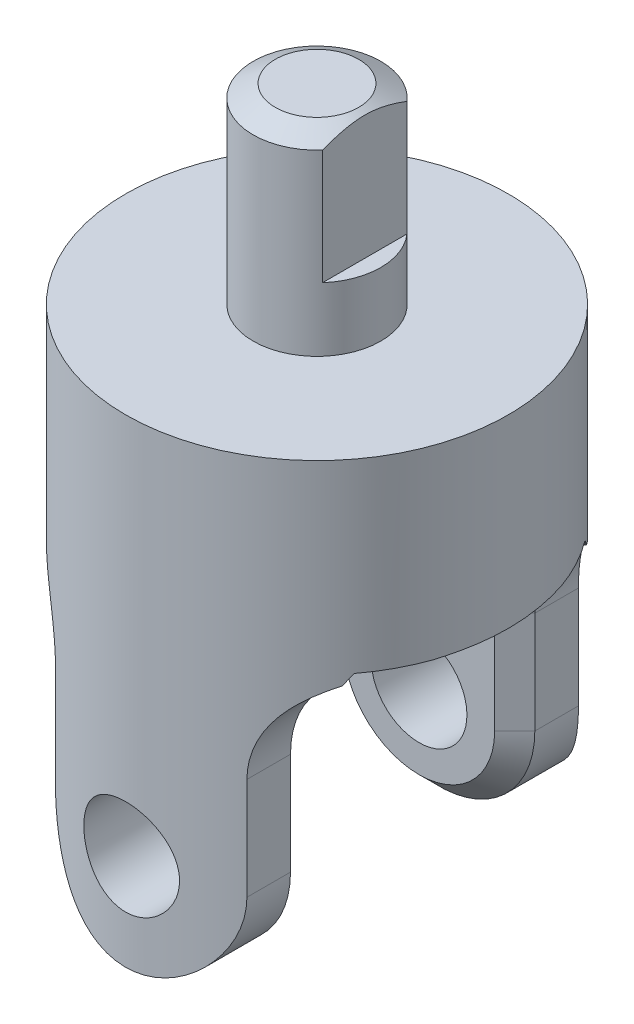
SolidWorks part; units mm, degrees
note: '?' marks a value the reader was unsure of.
ref_plane "Front" through (0, 0, 0) normal (0, 0, 1) x (1, 0, 0)
ref_plane "Top" through (0, 0, 0) normal (0, 1, 0) x (-1, 0, 0)
ref_plane "Right" through (0, 0, 0) normal (1, 0, 0) x (0, 0, -1)
sketch "Sketch1" plane through (0, 0, 0) normal (0, 1, 0) x (-1, 0, 0)
  circle A0 centre (0, 0) radius 19.05
  dimension "D1" = 38.1
extrude "Base-Extrude" add sketch "Sketch1" along normal blind 47.625
sketch "Sketch2" plane through (0, 0, 0) normal (0, 0, 1) x (1, 0, 0)
  line L0 (0, 0) -> (0, 23.7435) construction
  line L1 (9.525, 9.525) -> (9.525, 19.685)
  line L2 (-9.525, 9.525) -> (-9.525, 19.685)
  line L3 (19.05, 29.21) -> (19.05, -1.3662)
  line L4 (19.05, -1.3662) -> (-19.05, -1.3662)
  line L5 (-19.05, -1.3662) -> (-19.05, 29.21)
  line L6 (19.05, 0) -> (-19.05, 0) construction
  arc A0 (-9.525, 9.525) -> (9.525, 9.525) centre (0, 9.525) ccw
  arc A1 (9.525, 19.685) -> (19.05, 29.21) centre (19.05, 19.685) cw
  arc A2 (-9.525, 19.685) -> (-19.05, 29.21) centre (-19.05, 19.685) ccw
  dimension "D3" = 9.525
  dimension "D1" = 38.1
  dimension "D2" = 19.05
  dimension "D4" = 29.21
extrude "Cut-Extrude1" cut sketch "Sketch2" against normal through all and the other way through all
sketch "Sketch8" plane through (0, 0, 0) normal (1, 0, 0) x (0, 0, -1)
  line L0 (-10.16, -7.4553) -> (10.16, -7.4553)
  line L1 (-10.16, -7.4553) -> (-10.16, 29.1452)
  line L2 (10.16, 29.1452) -> (-10.16, 29.1452)
  line L3 (10.16, 29.1452) -> (10.16, -7.4553)
  point P4 (0, 0)
  dimension "D1" = 10.16
  dimension "D2" = 20.32
extrude "Cut-Extrude5" cut sketch "Sketch8" against normal through all and the other way blind 47.625
sketch "Sketch11" plane through (0, 0, 0) normal (0, 0, 1) x (1, 0, 0)
  circle A0 centre (0, 9.525) radius 4.7625
  dimension "D1" = 9.525
extrude "Cut-Extrude6" cut sketch "Sketch11" against normal through all and the other way through all
sketch "Sketch12" plane through (0, 47.625, 0) normal (0, 1, 0) x (-1, 0, 0)
  circle A0 centre (0, 0) radius 6.35
  dimension "D1" = 12.7
extrude "Boss-Extrude1" add sketch "Sketch12" along normal blind 19.05
chamfer "Chamfer3" distance 1.27 angle 60 1 edges at (0, 66.675, 6.35) first distance on face at (0, 66.675, 6.35)
ref_axis "Axis1" through (0, 97.625, 0) along (0, -1, 0)?
sketch "Sketch13" plane through (0, 66.675, 0) normal (0, 1, 0) x (-1, 0, 0)
  line L0 (-4.7625, 4.2001) -> (-4.7625, -4.2001)
  circle A0 centre (0, 0) radius 6.35 construction
  arc A1 (-4.7625, 4.2001) -> (-4.7625, -4.2001) centre (0, 0) ccw
  dimension "D1" = 1.5875
extrude "Cut-Extrude7" cut sketch "Sketch13" against normal blind 12.7
chamfer "Chamfer4" distance 2 angle 45 10 edges at (-11.3465, 25.287, -10.16) (-9.525, 14.605, -10.16) (0, 0, -10.16) (9.525, 14.605, -10.16) (11.3465, 25.287, -10.16) (-11.3465, 25.287, 10.16) (-9.525, 14.605, 10.16) (0, 0, 10.16) (9.525, 14.605, 10.16) (11.3465, 25.287, 10.16)
